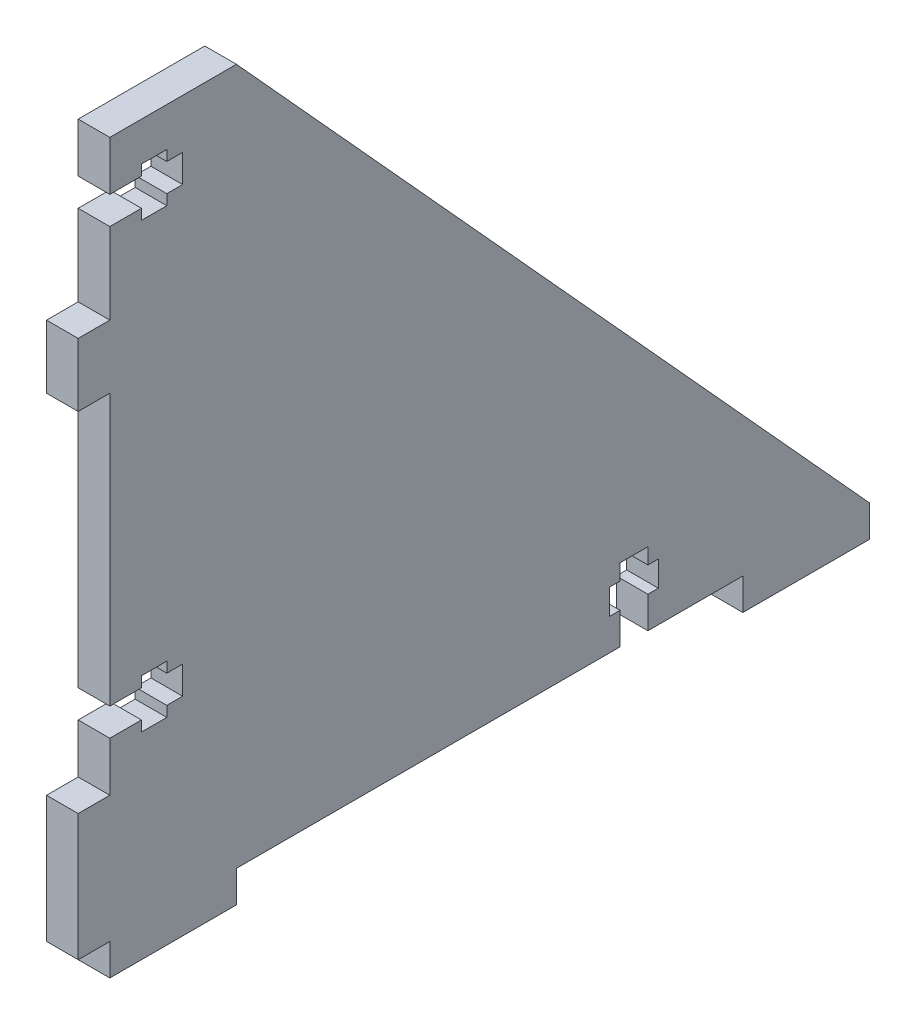
SolidWorks part; units mm, degrees
ref_plane "Front Plane" through (0, 0, 0) normal (0, 0, 1) x (1, 0, 0)
ref_plane "Top Plane" through (0, 0, 0) normal (0, 1, 0) x (1, 0, 0)
ref_plane "Right Plane" through (0, 0, 0) normal (1, 0, 0) x (0, 0, -1)
sketch "Sketch1" plane through (0, 0, 0) normal (1, 0, 0) x (0, 0, -1)
  line L0 (20, 110) -> (120, 0)
  line L1 (20, 0) -> (100, 0)
  line L2 (0, 0) -> (0, 110)
  line L3 (0, 110) -> (20, 110)
  line L5 (0, 0) -> (100, 0) construction
  line L6 (0, 97.8) -> (9, 103.85) construction
  line L7 (0, 0) -> (0, -5)
  line L8 (0, -5) -> (20, -5)
  line L9 (20, 0) -> (20, -5)
  line L10 (0, 102.2) -> (5, 102.2)
  line L11 (0, 32.2) -> (5, 32.2)
  line L12 (0, 27.8) -> (5, 27.8)
  line L13 (5, 32.2) -> (5, 27.8)
  line L14 (0, 102.2) -> (0, 97.8)
  line L15 (0, 97.8) -> (5, 97.8)
  line L16 (5, 102.2) -> (5, 97.8)
  line L17 (0, 20) -> (-5, 20)
  line L18 (0, 20) -> (0, 0)
  line L19 (0, 0) -> (-5, 0)
  line L20 (-5, 20) -> (-5, 0)
  line L21 (5, 103.85) -> (9, 103.85)
  line L22 (5, 103.85) -> (5, 96.15)
  line L23 (5, 96.15) -> (9, 96.15)
  line L24 (9, 103.85) -> (9, 96.15)
  line L25 (0, 102.2) -> (9, 96.15) construction
  line L26 (5, 96.15) -> (11.5, 102.2) construction
  line L27 (9, 102.2) -> (11.5, 102.2)
  line L28 (9, 102.2) -> (9, 97.8)
  line L29 (9, 97.8) -> (11.5, 97.8)
  line L30 (11.5, 102.2) -> (11.5, 97.8)
  line L31 (3.2727, 100) -> (9.1364, 100) construction
  line L32 (5, 103.85) -> (11.5, 97.8) construction
  line L33 (5, 33.85) -> (9, 33.85)
  line L34 (5, 33.85) -> (5, 26.15)
  line L35 (5, 26.15) -> (9, 26.15)
  line L36 (9, 33.85) -> (9, 26.15)
  line L37 (9, 32.2) -> (11.5, 32.2)
  line L38 (9, 32.2) -> (9, 27.8)
  line L39 (9, 27.8) -> (11.5, 27.8)
  line L40 (11.5, 32.2) -> (11.5, 27.8)
  line L41 (0, 27.8) -> (9, 33.85) construction
  line L42 (0, 32.2) -> (9, 26.15) construction
  line L43 (5, 26.15) -> (11.5, 32.2) construction
  line L44 (3.2727, 30) -> (9.1364, 30) construction
  line L45 (5, 33.85) -> (11.5, 27.8) construction
  line L46 (0, 102.2) -> (0, 32.2) construction
  line L47 (78.95, 9) -> (85, 0) construction
  line L48 (80.6, 0) -> (85, 0)
  line L49 (80.6, 0) -> (80.6, 5)
  line L50 (80.6, 5) -> (85, 5)
  line L51 (85, 0) -> (85, 5)
  line L52 (78.95, 9) -> (86.65, 9)
  line L53 (78.95, 9) -> (78.95, 5)
  line L54 (78.95, 5) -> (86.65, 5)
  line L55 (86.65, 9) -> (86.65, 5)
  line L56 (80.6, 0) -> (86.65, 9) construction
  line L57 (78.95, 5) -> (85, 11.5) construction
  line L58 (80.6, 11.5) -> (85, 11.5)
  line L59 (80.6, 11.5) -> (80.6, 9)
  line L60 (80.6, 9) -> (85, 9)
  line L61 (85, 11.5) -> (85, 9)
  line L62 (86.65, 5) -> (80.6, 11.5) construction
  line L63 (82.8, 3.2727) -> (82.8, 9.1364) construction
  line L65 (0, 85) -> (-5, 85)
  line L66 (0, 85) -> (0, 75)
  line L67 (0, 75) -> (-5, 75)
  line L68 (-5, 85) -> (-5, 75)
  line L69 (100, 0) -> (120, 0) construction
  line L70 (100, 0) -> (100, -5)
  line L71 (100, -5) -> (120, -5)
  line L72 (120, 0) -> (120, -5)
  dimension "D1" = 100
  dimension "D2" = 110
  dimension "D3" = 20
  dimension "D4" = 15
  dimension "D5" = 5
  dimension "D6" = 5
  dimension "D7" = 20
  dimension "D8" = 5
  dimension "D9" = 4.4
  dimension "D10" = 10
  dimension "D11" = 20
  dimension "D12" = 2
  dimension "D13" = 7.7
  dimension "D14" = 4
  dimension "D15" = 4.4
  dimension "D16" = 2.5
  dimension "D17" = 70
  dimension "D18" = 5
  dimension "D19" = 4.4
  dimension "D20" = 7.7
  dimension "D21" = 4
  dimension "D22" = 2.5
  dimension "D23" = 4.4
  dimension "D25" = 5
  dimension "D26" = 10
  dimension "D27" = 25
  dimension "D28" = 10
  dimension "D29" = 5
  dimension "D30" = 20
extrude "Boss-Extrude1" add sketch "Sketch1" along normal blind 5 contours L58 L61 L52 L55 L54 L51 L1 L0 L3 L2 L10 L22 L21 L24 L27 L30 L29 L23 L15 L11 L34 L33 L36 L37 L40 L39 L35 L12 L17 L20 L19 L7 L8 L9 L49 L53 L59 | L17 L20 L19 L2 | L65 L68 L67 L2 region at (0, 40.6675, -41.6786) region at (0, 80, 2.5) region at (0, 10, 2.5)
